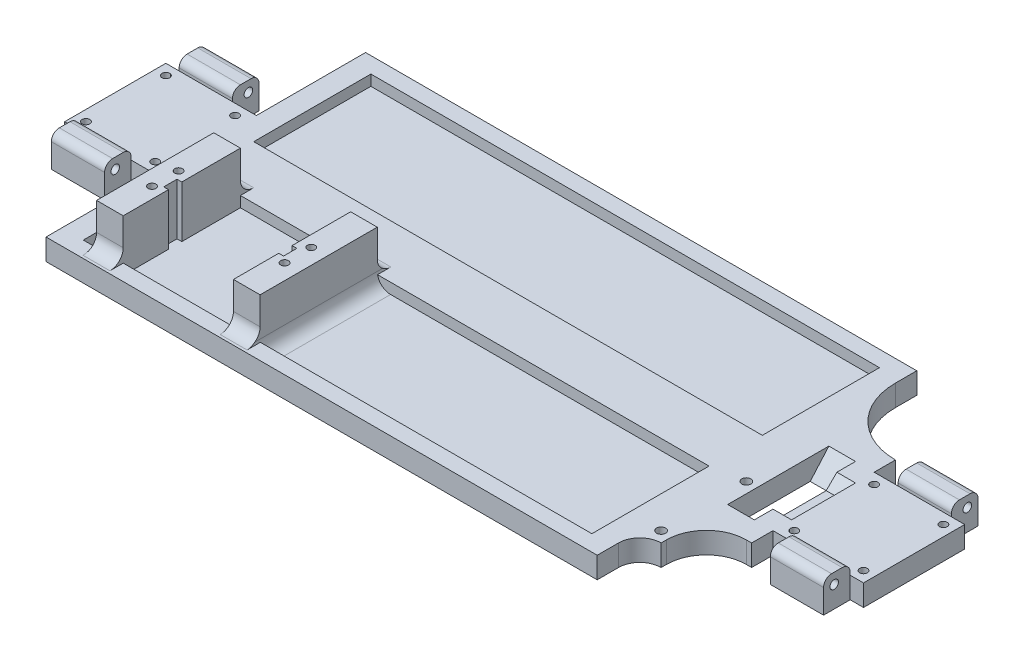
SolidWorks part; units mm, degrees
ref_plane "Front" through (0, 0, 0) normal (0, 0, 1) x (1, 0, 0)
ref_plane "Top" through (0, 0, 0) normal (0, 1, 0) x (1, 0, 0)
ref_plane "Right" through (0, 0, 0) normal (1, 0, 0) x (0, 0, -1)
sketch "Sketch1" plane through (0, 0, 0) normal (0, 1, 0) x (1, 0, 0)
  line L1 (0, 0) -> (300, 0)
  line L2 (0, 0) -> (0, -20)
  line L3 (0, -20) -> (300, -20)
  line L4 (300, 0) -> (300, -20)
  dimension "D1" = 20
  dimension "D2" = 300
extrude "Boss-Extrude1" add sketch "Sketch1" along normal blind 8
sketch "Sketch2" plane through (0, 0, 20) normal (0, 0, 1) x (1, 0, 0)
  line L0 (0, 8) -> (300, 8) construction
  line L1 (0, 0) -> (34, 0)
  line L2 (0, 0) -> (0, 8)
  line L3 (0, 8) -> (34, 8)
  line L4 (34, 0) -> (34, 8)
  line L5 (266, 8) -> (300, 8)
  line L6 (300, 0) -> (300, 8)
  line L7 (266, 0) -> (300, 0)
  line L8 (266, 0) -> (266, 8)
  dimension "D1" = 34
  dimension "D2" = 2
extrude "Boss-Extrude2" add sketch "Sketch2" along normal blind 9
sketch "Sketch3" plane through (0, 0, 0) normal (0, 0, -1) x (-1, 0, 0)
  line L0 (-300, 8) -> (0, 8) construction
  line L1 (0, 0) -> (-34, 0)
  line L2 (0, 0) -> (0, 8)
  line L3 (0, 8) -> (-34, 8)
  line L4 (-34, 0) -> (-34, 8)
  line L5 (-300, 0) -> (-300, 8)
  line L6 (-266, 8) -> (-300, 8)
  line L7 (-266, 0) -> (-266, 8)
  line L8 (-266, 0) -> (-300, 0)
  dimension "D1" = 34
  dimension "D2" = 2
extrude "Boss-Extrude3" add sketch "Sketch3" along normal blind 9
sketch "Sketch4" plane through (0, 8, 0) normal (0, 1, 0) x (1, 0, 0)
  line L0 (0, 9) -> (34, 9) construction
  line L1 (0, 9) -> (0, -29) construction
  circle A0 centre (4, 5) radius 1.45
  circle A1 centre (30, 5) radius 1.45
  circle A2 centre (30, -25) radius 1.45
  circle A3 centre (4, -25) radius 1.45
  circle A4 centre (296, -25) radius 1.45
  circle A5 centre (296, 5) radius 1.45
  circle A6 centre (270, -25) radius 1.45
  circle A7 centre (270, 5) radius 1.45
  dimension "D1" = 2.9
  dimension "D2" = 4
  dimension "D3" = 4
  dimension "D4" = 2
  dimension "D5" = 2
  dimension "D6" = 2
extrude "Cut-Extrude1" cut sketch "Sketch4" against normal through all
sketch "Sketch5" plane through (0, 0, 20) normal (0, 0, 1) x (1, 0, 0)
  line L0 (34, 8) -> (266, 8) construction
  line L1 (266, 0) -> (241, 0)
  line L2 (266, 0) -> (266, 8)
  line L3 (266, 8) -> (241, 8)
  line L4 (241, 0) -> (241, 8)
  dimension "D1" = 25
extrude "Boss-Extrude4" add sketch "Sketch5" along normal blind 17
sketch "Sketch6" plane through (0, 0, 0) normal (0, 0, -1) x (-1, 0, 0)
  line L0 (-266, 0) -> (-34, 0) construction
  line L1 (-266, 8) -> (-241, 8)
  line L2 (-266, 8) -> (-266, 0)
  line L3 (-266, 0) -> (-241, 0)
  line L4 (-241, 8) -> (-241, 0)
  dimension "D1" = 25
extrude "Boss-Extrude5" add sketch "Sketch6" along normal blind 17
sketch "Sketch7" plane through (0, 8, 0) normal (0, 1, 0) x (1, 0, 0)
  line L0 (266, -37) -> (241, -37) construction
  line L1 (259, -29) -> (249, -29)
  line L2 (259, -29) -> (259, 9)
  line L3 (259, 9) -> (249, 9)
  line L4 (249, -29) -> (249, 9)
  line L5 (241, -37) -> (241, -20) construction
  dimension "D1" = 10
  dimension "D2" = 38
  dimension "D3" = 8
  dimension "D4" = 8
extrude "Cut-Extrude2" cut sketch "Sketch7" against normal through all
sketch "Sketch8" plane through (0, 8, 0) normal (0, 1, 0) x (1, 0, 0)
  line L0 (259, -29) -> (259, 9) construction
  line L1 (259, -18) -> (266, -18)
  line L2 (259, -18) -> (259, -2)
  line L3 (259, -2) -> (266, -2)
  line L4 (266, -18) -> (266, -2)
  line L5 (266, -37) -> (241, -37) construction
  dimension "D1" = 7
  dimension "D2" = 16
  dimension "D3" = 19
extrude "Cut-Extrude3" cut sketch "Sketch8" against normal blind 4
sketch "Sketch9" plane through (259, 0, 0) normal (-1, 0, 0) x (0, 0, 1)
  line L0 (18, 4) -> (22, 8)
  line L1 (29, 8) -> (18, 8) construction
  line L2 (22, 8) -> (18, 8)
  line L3 (18, 8) -> (18, 4)
  line L4 (2, 4) -> (-2, 8)
  line L5 (2, 8) -> (-9, 8) construction
  line L6 (-2, 8) -> (2, 8)
  line L7 (2, 8) -> (2, 4)
  dimension "D1" = 4
  dimension "D2" = 4
extrude "Cut-Extrude4" cut sketch "Sketch9" against normal blind 7
sketch "Sketch10" plane through (259, 0, 0) normal (-1, 0, 0) x (0, 0, 1)
  line L0 (-9, 8) -> (-2, 0)
  line L1 (29, 0) -> (-9, 0) construction
  line L2 (-2, 0) -> (-9, 0)
  line L3 (-9, 0) -> (-9, 8)
  line L4 (29, 8) -> (22, 0)
  line L5 (22, 0) -> (29, 0)
  line L6 (29, 0) -> (29, 8)
  line L7 (-51.4523, 12.1971) -> (-51.8778, 12.5861)
  line M6 (-9, 8) -> (-9, 0)
  line M7 (-9, 0) -> (29, 0)
  line M8 (29, 0) -> (29, 8)
  dimension "D1" = 7
  dimension "D2" = 7
extrude "Boss-Extrude6" add sketch "Sketch10" along normal blind 10 contours L0 M6 M7 | L4 M8 M7 region at (259, 2.6667, 26.6667) region at (259, 2.6667, -6.6667)
sketch "Sketch12" plane through (0, 0, 37) normal (0, 0, 1) x (1, 0, 0)
  line L0 (241, 0) -> (266, 0) construction
  line L1 (241, 8) -> (249, 8)
  line L2 (241, 8) -> (241, 0)
  line L3 (241, 0) -> (249, 0)
  line L4 (249, 8) -> (249, 0)
  dimension "D1" = 8
extrude "Boss-Extrude7" add sketch "Sketch12" along normal blind 17
sketch "Sketch13" plane through (0, 8, 0) normal (0, 1, 0) x (1, 0, 0)
  line L0 (249, -54) -> (241, -54) construction
  line L1 (249, -54) -> (249, -37) construction
  circle A0 centre (245, -50) radius 1.7
  circle A1 centre (245, -18) radius 1.7
  dimension "D1" = 3.4
  dimension "D2" = 4
  dimension "D3" = 4
  dimension "D4" = 2
extrude "Cut-Extrude6" cut sketch "Sketch13" against normal through all
sketch "Sketch14" plane through (0, 0, 29) normal (0, 0, 1) x (1, 0, 0)
  line L1 (295, 12) -> (275, 12)
  line L2 (295, 12) -> (295, 0)
  line L3 (295, 0) -> (275, 0)
  line L4 (275, 12) -> (275, 0)
  line L5 (266, 0) -> (300, 0) construction
  line L7 (266, 8) -> (266, 0) construction
  dimension "D1" = 20
  dimension "D2" = 9
  dimension "D3" = 12
extrude "Boss-Extrude8" add sketch "Sketch14" along normal blind 10
sketch "Sketch15" plane through (295, 0, 0) normal (1, 0, 0) x (0, 0, -1)
  line L0 (-39, 0) -> (-39, 12) construction
  line L1 (-39, 12) -> (-29, 12) construction
  circle A0 centre (-35, 8) radius 1.6
  dimension "D1" = 3.2
  dimension "D2" = 4
  dimension "D3" = 4
extrude "Cut-Extrude7" cut sketch "Sketch15" against normal blind 20
sketch "Sketch16" plane through (0, 0, -9) normal (0, 0, -1) x (-1, 0, 0)
  line L1 (-295, 12) -> (-275, 12)
  line L2 (-295, 12) -> (-295, 0)
  line L3 (-295, 0) -> (-275, 0)
  line L4 (-275, 12) -> (-275, 0)
  line L5 (-300, 0) -> (-266, 0) construction
  line L6 (-266, 0) -> (-266, 8) construction
  dimension "D1" = 20
  dimension "D2" = 9
  dimension "D3" = 12
extrude "Boss-Extrude9" add sketch "Sketch16" along normal blind 10
sketch "Sketch17" plane through (295, 0, 0) normal (1, 0, 0) x (0, 0, -1)
  line L1 (19, 12) -> (19, 0) construction
  line L2 (19, 12) -> (9, 12) construction
  circle A0 centre (15, 8) radius 1.6
  dimension "D1" = 3.2
  dimension "D2" = 4
  dimension "D3" = 4
extrude "Cut-Extrude8" cut sketch "Sketch17" against normal blind 20
sketch "Sketch18" plane through (0, 0, -9) normal (0, 0, -1) x (-1, 0, 0)
  line L1 (-25, 12) -> (-5, 12)
  line L2 (-25, 12) -> (-25, 0)
  line L3 (-25, 0) -> (-5, 0)
  line L4 (-5, 12) -> (-5, 0)
  line L5 (-34, 0) -> (0, 0) construction
  line L6 (-34, 8) -> (-34, 0) construction
  dimension "D1" = 20
  dimension "D2" = 9
  dimension "D3" = 12
extrude "Boss-Extrude10" add sketch "Sketch18" along normal blind 10
sketch "Sketch19" plane through (5, 0, 0) normal (-1, 0, 0) x (0, 0, 1)
  line L0 (-19, 0) -> (-19, 12) construction
  line L1 (-19, 12) -> (-9, 12) construction
  circle A0 centre (-15, 8) radius 1.6
  dimension "D1" = 3.2
  dimension "D2" = 4
  dimension "D3" = 4
extrude "Cut-Extrude9" cut sketch "Sketch19" against normal blind 20
sketch "Sketch20" plane through (0, 0, 29) normal (0, 0, 1) x (1, 0, 0)
  line L1 (5, 12) -> (25, 12)
  line L2 (5, 12) -> (5, 0)
  line L3 (5, 0) -> (25, 0)
  line L4 (25, 12) -> (25, 0)
  line L5 (0, 0) -> (34, 0) construction
  line L6 (34, 0) -> (34, 8) construction
  dimension "D1" = 20
  dimension "D2" = 9
  dimension "D3" = 12
extrude "Boss-Extrude11" add sketch "Sketch20" along normal blind 10
sketch "Sketch21" plane through (5, 0, 0) normal (-1, 0, 0) x (0, 0, 1)
  line L0 (39, 12) -> (39, 0) construction
  line L2 (39, 12) -> (29, 12) construction
  circle A0 centre (35, 8) radius 1.6
  dimension "D1" = 3.2
  dimension "D2" = 4
  dimension "D3" = 4
extrude "Cut-Extrude10" cut sketch "Sketch21" against normal blind 20
sketch "Sketch22" plane through (0, 0, 0) normal (0, -1, 0) x (-1, 0, 0)
  line L0 (-34, -20) -> (-241, -20) construction
  line L1 (-34, -20) -> (-241, -20)
  line L2 (-34, -20) -> (-34, -70)
  line L3 (-34, -70) -> (-241, -70)
  line L4 (-241, -20) -> (-241, -70)
  line L5 (-34, 9) -> (-34, 0) construction
  line L6 (-34, 0) -> (-241, 0)
  line L7 (-34, 0) -> (-34, 50)
  line L8 (-34, 50) -> (-241, 50)
  line L9 (-241, 0) -> (-241, 50)
  line L10 (-241, 0) -> (-34, 0) construction
  dimension "D1" = 50
  dimension "D2" = 50
extrude "Boss-Extrude12" add sketch "Sketch22" against normal blind 8
sketch "Sketch23" plane through (0, 8, 0) normal (0, 1, 0) x (1, 0, 0)
  line L0 (241, -70) -> (34, -70) construction
  line L1 (233, -64) -> (42, -64)
  line L2 (233, -64) -> (233, -20)
  line L3 (233, -20) -> (42, -20)
  line L4 (42, -64) -> (42, -20)
  line L5 (233, 44) -> (42, 44)
  line L6 (233, 44) -> (233, 0)
  line L7 (233, 0) -> (42, 0)
  line L8 (42, 44) -> (42, 0)
  line L9 (241, -54) -> (241, -70) construction
  line L10 (34, -70) -> (34, -29) construction
  line L11 (34, 9) -> (34, 50) construction
  line L12 (34, 50) -> (241, 50) construction
  line L13 (241, 50) -> (241, 17) construction
  dimension "D1" = 6
  dimension "D2" = 8
  dimension "D3" = 8
  dimension "D4" = 44
  dimension "D5" = 8
  dimension "D6" = 44
  dimension "D7" = 6
  dimension "D8" = 8
extrude "Cut-Extrude11" cut sketch "Sketch23" against normal blind 4
sketch "Sketch24" plane through (0, 4, 0) normal (0, 1, 0) x (1, 0, 0)
  line L0 (233, -20) -> (42, -20) construction
  line L1 (98.4, -20) -> (108.4, -20)
  line L2 (98.4, -20) -> (98.4, -64)
  line L3 (98.4, -64) -> (108.4, -64)
  line L4 (108.4, -20) -> (108.4, -64)
  line L5 (42, -64) -> (233, -64) construction
  line L7 (42, -20) -> (42, -64) construction
  line L8 (42, -20) -> (42, -64) construction
  line L9 (47, -20) -> (57, -20)
  line L10 (47, -20) -> (47, -64)
  line L11 (47, -64) -> (57, -64)
  line L12 (57, -20) -> (57, -64)
  dimension "D1" = 10
  dimension "D2" = 56.4
  dimension "D3" = 10
  dimension "D4" = 5
extrude "Boss-Extrude14" add sketch "Sketch24" along normal blind 19.4
sketch "Sketch25" plane through (0, 23.4, 0) normal (0, 1, 0) x (1, 0, 0)
  line L2 (47, -64) -> (57, -64) construction
  line L4 (98.4, -20) -> (98.4, -64) construction
  line L5 (98.4, -64) -> (108.4, -64) construction
  line L6 (57, -64) -> (57, -20) construction
  circle A0 centre (102.6, -49) radius 1.45
  circle A1 centre (102.6, -39) radius 1.45
  circle A2 centre (52.8, -49) radius 1.45
  circle A3 centre (52.8, -39) radius 1.45
  dimension "D1" = 2.9
  dimension "D2" = 2.9
  dimension "D3" = 2.9
  dimension "D4" = 2.9
  dimension "D5" = 10
  dimension "D6" = 10
  dimension "D7" = 4.2
  dimension "D8" = 4.2
  dimension "D9" = 15
  dimension "D10" = 4.2
  dimension "D11" = 4.2
  dimension "D12" = 15
extrude "Cut-Extrude12" cut sketch "Sketch25" against normal blind 15
fillet "Fillet1" radius 5 4 edges at (52, 8, 20) (103.4, 8, 20) (103.4, 8, 64) (52, 8, 64)
fillet "Fillet2" radius 5 2 edges at (47, 4, 42) (108.4, 4, 42)
fillet "Fillet3" radius 8 1 edges at (241, 4, 54)
fillet "Fillet4" radius 15 1 edges at (249, 4, 37)
fillet "Fillet5" radius 25 1 edges at (241, 4, -17)
fillet "Fillet6" radius 3 8 edges at (15, 12, 39) (15, 12, 29) (15, 12, -9) (15, 12, -19) (285, 12, 39) (285, 12, 29) (285, 12, -9) (285, 12, -19)
sketch "Sketch27" plane through (0, 23.4, 0) normal (0, 1, 0) x (1, 0, 0)
  line L0 (57, -64) -> (57, -20) construction
  line L1 (57, -47) -> (55.2, -47)
  line L2 (57, -47) -> (57, -42)
  line L3 (57, -42) -> (55.2, -42)
  line L4 (55.2, -47) -> (55.2, -42)
  line L5 (98.4, -20) -> (98.4, -64) construction
  line L6 (98.4, -47) -> (100.2, -47)
  line L7 (98.4, -47) -> (98.4, -42)
  line L8 (98.4, -42) -> (100.2, -42)
  line L9 (100.2, -47) -> (100.2, -42)
  line L10 (98.4, -64) -> (108.4, -64) construction
  line L11 (47, -64) -> (57, -64) construction
  dimension "D1" = 5
  dimension "D2" = 5
  dimension "D3" = 1.8
  dimension "D4" = 1.8
  dimension "D5" = 17
  dimension "D6" = 17
extrude "Cut-Extrude13" cut sketch "Sketch27" against normal blind 19.4
